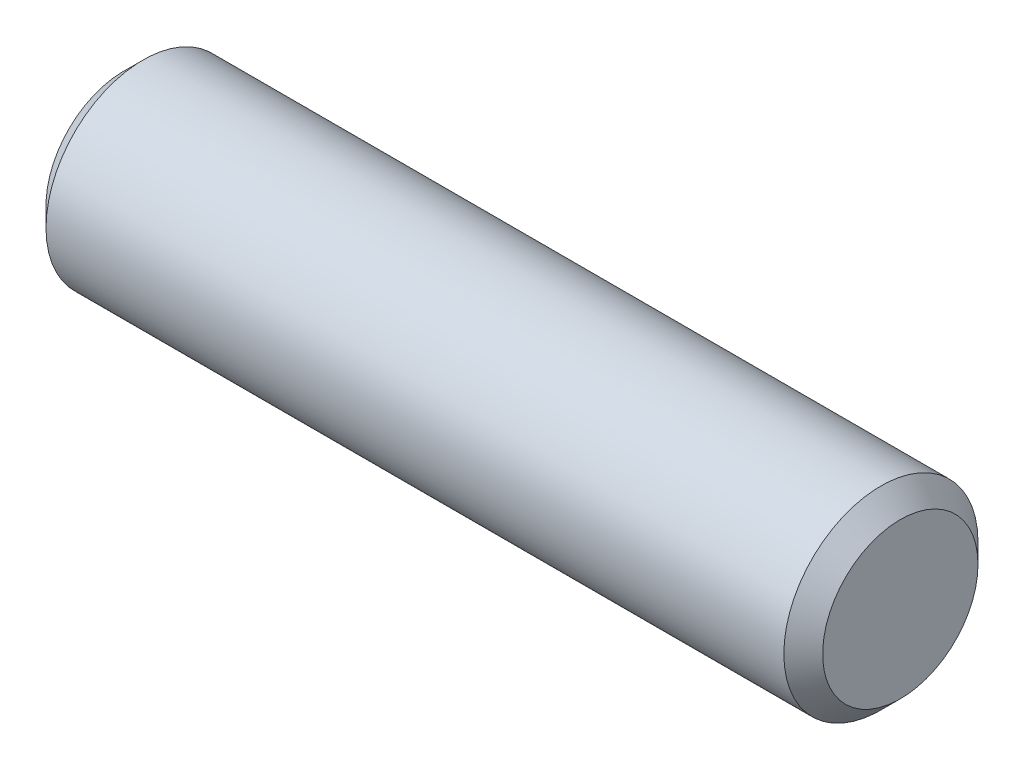
SolidWorks part; units mm, degrees
material "Cast Alloy Steel"
ref_plane "Front" through (0, 0, 0) normal (0, 0, 1) x (1, 0, 0)
ref_plane "Top" through (0, 0, 0) normal (0, 1, 0) x (1, 0, 0)
ref_plane "Right" through (0, 0, 0) normal (1, 0, 0) x (0, 0, -1)
sketch "Sketch1" plane through (0, 0, 0) normal (0, 0, 1) x (1, 0, 0)
  line L0 (-6.35, 0) -> (6.35, 0) construction
  line L1 (6.35, 1.5875) -> (6.35, -1.5875) construction
  line L2 (-6.35, 1.5875) -> (-6.35, -1.5875) construction
  dimension "Length" = 12.7
  dimension "Diameter" = 3.175
sketch "Sketch2" plane through (0, 0, 0) normal (1, 0, 0) x (0, 0, -1)
  circle A0 centre (0, 0) radius 1.5875
extrude "Extrude1" add sketch "Sketch2" against normal up to vertex (6.35 mm away) and the other way up to vertex (6.35 mm away) up to point (-6.35, 1.5875, 0) other way up to point (6.35, 1.5875, 0)
chamfer "Chamfer1" distance 0.3175 angle 45 2 edges at (6.35, 0, -1.5875) (-6.35, 0, -1.5875)
equation "\"D1@Chamfer1\" = \"Diameter@Sketch1\"*.1"
